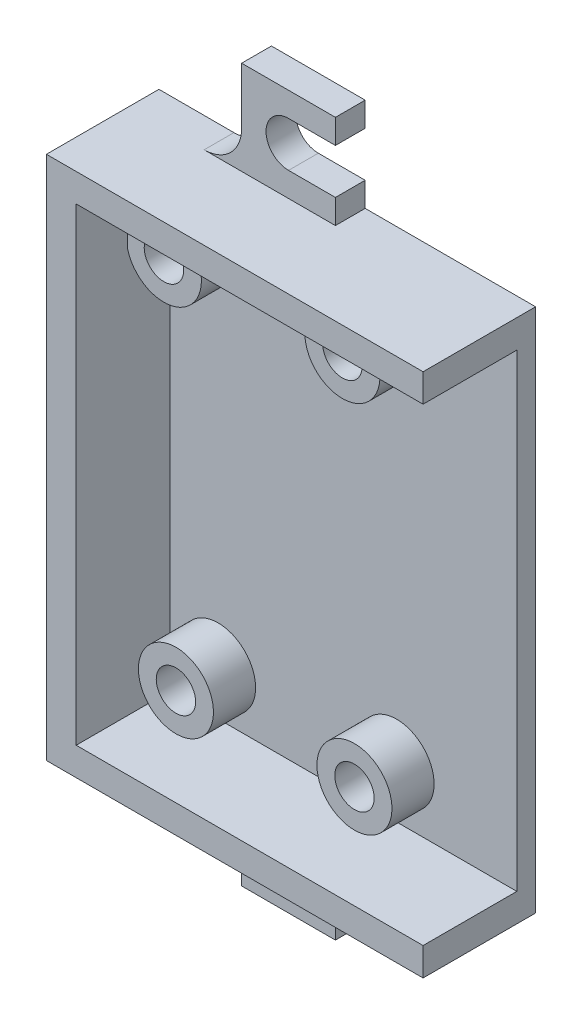
SolidWorks part; units mm, degrees
material "ABS"
ref_plane "X-Y Datum" through (0, 0, 0) normal (0, 0, 1) x (1, 0, 0)
ref_plane "X-Z Datum" through (0, 0, 0) normal (0, 1, 0) x (1, 0, 0)
ref_plane "Y-Z Datum" through (0, 0, 0) normal (1, 0, 0) x (0, 0, -1)
sketch "Sketch1" plane through (0, 0, 2000) normal (0, 0, -1) x (-1, 0, 0)
  circle A0 centre (-578.4497, -1208.5941) radius 2.1 construction
  circle A1 centre (-597.4895, -1207.9709) radius 2.1 construction
  circle A2 centre (-577.1659, -1169.3721) radius 2.1 construction
  circle A3 centre (-596.2057, -1168.7489) radius 2.1 construction
  circle A4 centre (-578.4497, -1208.5941) radius 2.1
  circle A5 centre (-597.4895, -1207.9709) radius 2.1
  circle A6 centre (-577.1659, -1169.3721) radius 2.1
  circle A7 centre (-596.2057, -1168.7489) radius 2.1
  circle A8 centre (-596.2057, -1168.7489) radius 4
  circle A9 centre (-577.1659, -1169.3721) radius 4
  circle A10 centre (-597.4895, -1207.9709) radius 4
  circle A11 centre (-578.4497, -1208.5941) radius 4
  dimension "D1" = 8
  dimension "D2" = 8
  dimension "D3" = 8
  dimension "D4" = 8
extrude "Boss-Extrude1" add sketch "Sketch1" along normal blind 4.5
sketch "Sketch2" plane through (0, 0, 1995.5) normal (0, 0, -1) x (-1, 0, 0)
  line L0 (-573.2383, -1189.1327) -> (-610.3818, -1187.8045) construction
  line L1 (-573.8801, -1208.7437) -> (-572.5964, -1169.5217) construction
  line L2 (-609.878, -1172.4127) -> (-610.8856, -1203.1962) construction
  line L4 (-610.31, -1216.4686) -> (-573.31, -1216.4686)
  line L5 (-610.31, -1216.4686) -> (-610.31, -1160.4686)
  line L6 (-610.31, -1160.4686) -> (-573.31, -1160.4686)
  line L7 (-573.31, -1216.4686) -> (-573.31, -1160.4686)
  line L8 (-610.31, -1216.4686) -> (-573.31, -1160.4686) construction
  line L9 (-610.31, -1160.4686) -> (-573.31, -1216.4686) construction
  line L10 (-610.31, -1160.4686) -> (-573.31, -1160.4686)
  line L11 (-610.31, -1160.4686) -> (-610.31, -1163.4686)
  line L12 (-610.31, -1163.4686) -> (-573.31, -1163.4686)
  line L13 (-573.31, -1160.4686) -> (-573.31, -1163.4686)
  line L14 (-610.31, -1216.4686) -> (-573.31, -1216.4686)
  line L15 (-610.31, -1216.4686) -> (-610.31, -1213.4686)
  line L16 (-610.31, -1213.4686) -> (-573.31, -1213.4686)
  line L17 (-573.31, -1216.4686) -> (-573.31, -1213.4686)
  line L18 (-573.31, -1160.4686) -> (-570.135, -1160.4686)
  line L19 (-573.31, -1160.4686) -> (-573.31, -1216.4686)
  line L20 (-573.31, -1216.4686) -> (-570.135, -1216.4686)
  line L21 (-570.135, -1160.4686) -> (-570.135, -1216.4686)
  point P6 (-591.81, -1188.4686)
  circle M20 centre (-596.2057, -1168.7489) radius 4
  circle M21 centre (-596.2057, -1168.7489) radius 2.1
  dimension "D1" = 56
  dimension "D2" = 37
  dimension "D3" = 3
  dimension "D4" = 3
  dimension "D5" = 3.175
extrude "Boss-Extrude2" add sketch "Sketch2" along normal blind 2 contours L5 L16 L7 L12 | M21 | M20 M21 region at (591.6873, -1189.0193, 1995.5) region at (600.0926, -1168.7489, 1995.5) region at (596.2057, -1168.7489, 1995.5)
extrude "Boss-Extrude3" add sketch "Sketch2<5>" along normal blind 2 and the other way blind 10 contours L5 L12 L7 L6 | L16 L5 L4 L7 region at (591.81, -1214.9686, 1995.5) region at (591.81, -1161.9686, 1995.5)
sketch "Sketch2<5>" plane through (0, 0, 1995.5) normal (0, 0, -1) x (-1, 0, 0) same geometry as "Sketch2"
extrude "Boss-Extrude4" add sketch "Sketch2<6>" against normal blind 10 and the other way blind 2 contours L21 L18 L7 L20 region at (571.7225, -1188.4686, 1995.5)
sketch "Sketch2<6>" plane through (0, 0, 1995.5) normal (0, 0, -1) x (-1, 0, 0) same geometry as "Sketch2"
sketch "Sketch3" plane through (0, 0, 1993.5) normal (0, 0, -1) x (-1, 0, 0)
  line L0 (-610.31, -1160.4686) -> (-570.135, -1160.4686) construction
  line L1 (-582.135, -1160.4686) -> (-592.135, -1160.4686)
  line L2 (-582.135, -1160.4686) -> (-582.135, -1150.4686)
  line L3 (-582.135, -1150.4686) -> (-592.135, -1150.4686)
  line L4 (-592.135, -1160.4686) -> (-592.135, -1150.4686)
  line L5 (-570.135, -1160.4686) -> (-570.135, -1216.4686) construction
  line L6 (-587.135, -1150.4686) -> (-587.135, -1160.4686) construction
  circle A0 centre (-587.135, -1155.4686) radius 2
  line M7 (-570.135, -1160.4686) -> (-610.31, -1160.4686)
  dimension "D4" = 4
  dimension "D1" = 10
  dimension "D2" = 10
  dimension "D3" = 12
extrude "Boss-Extrude5" add sketch "Sketch3" against normal blind 3.175 contours L3 L6 A0 L2 M7 | L6 L3 L4 region at (584.3977, -1155.4686, 1993.5) region at (589.8723, -1155.4686, 1993.5)
ref_plane "Plane1" through (0, -1188.4686, 0) normal (0, -1, 0) x (-1, 0, 0)
mirror "Mirror1" about plane through (0, -1188.4686, 0) normal (0, -1, 0) of "Boss-Extrude5"
hole_wizard "M4 Clearance Hole3" positions "Sketch15" profile "Sketch14" hole size "M4" standard "ANSI Metric" end condition up to next
sketch "Sketch15" plane through (0, 0, 1996.675) normal (0, 0, 1) x (1, 0, 0)
  point P0 (587.135, -1155.4686)
  point P3 (587.135, -1221.4686)
sketch "Sketch14" plane through (587.135, -1155.4686, 1996.675) normal (1, 0, 0) x (0, -1, 0)
  line L0 (0, 0) -> (0, 3.175)
  line L1 (0, 3.175) -> (2.4, 3.175)
  line L2 (2.4, 3.175) -> (2.4, 0)
  line L5 (2.4, 0) -> (0, 0)
  line L11 (0, -6.35) -> (0, 107.95) construction
  dimension "Thru Hole Dia." = 4.8
  dimension "Thru Hole Depth" = 3.175
sketch "Sketch16" plane through (0, 0, 1996.675) normal (0, 0, 1) x (1, 0, 0)
  line L0 (587.135, -1153.0686) -> (592.135, -1153.0686)
  line L1 (592.135, -1160.4686) -> (592.135, -1150.4686) construction
  line L2 (587.135, -1157.8686) -> (592.135, -1157.8686)
  line L3 (587.135, -1219.0686) -> (592.135, -1219.0686)
  line L4 (592.135, -1216.4686) -> (592.135, -1226.4686) construction
  line L5 (587.135, -1223.8686) -> (592.135, -1223.8686)
  line L6 (592.135, -1223.8686) -> (592.135, -1219.0686)
  line L7 (592.135, -1153.0686) -> (592.135, -1157.8686)
  circle A0 centre (587.135, -1155.4686) radius 2.4 construction
  circle A1 centre (587.135, -1221.4686) radius 2.4 construction
  circle A2 centre (587.135, -1155.4686) radius 2.4
  circle A3 centre (587.135, -1221.4686) radius 2.4
  line M8 (592.135, -1160.4686) -> (592.135, -1150.4686)
  circle M9 centre (587.135, -1155.4686) radius 2.4
  dimension "D1" = 5
  dimension "D2" = 5
  dimension "D3" = 5
  dimension "D4" = 5
extrude "Cut-Extrude1" cut sketch "Sketch16" against normal blind 10 contours L2 L0 M9 M8 | A3 L5 L6 L3 region at (590.5314, -1155.4686, 1996.675) region at (590.5314, -1221.4686, 1996.675)
fillet "Fillet1" radius 4 2 edges at (582.135, -1216.4686, 1995.0875) (582.135, -1160.4686, 1995.0875)
